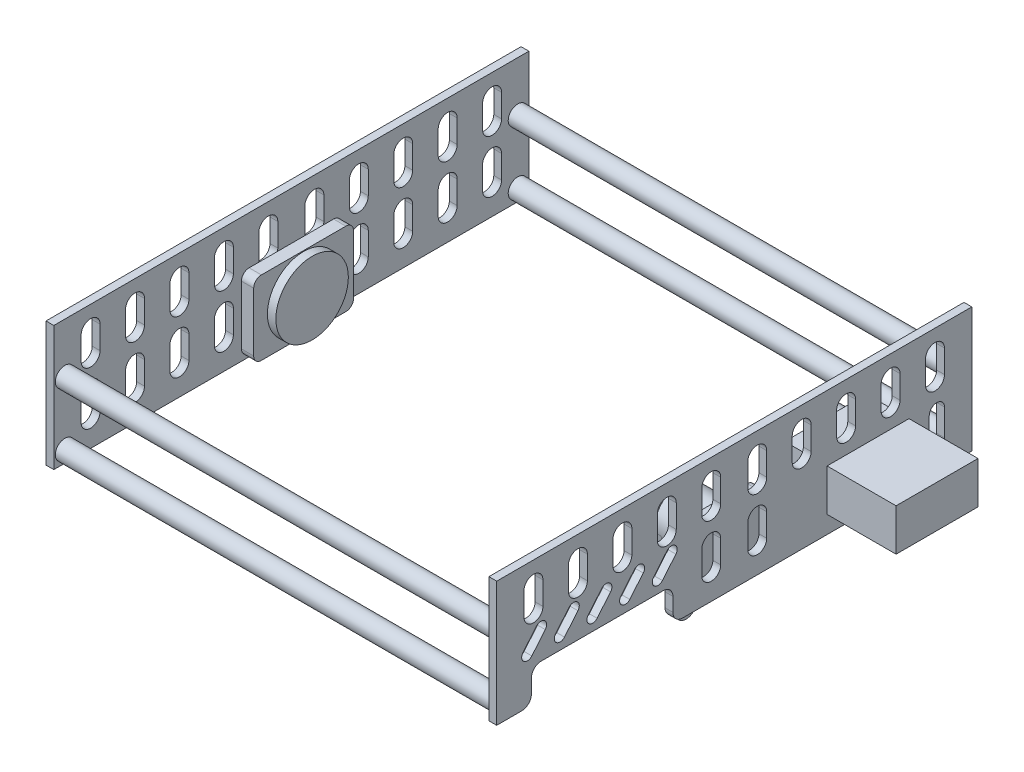
SolidWorks part; units mm, degrees
ref_plane "Front Plane" through (0, 0, 0) normal (0, 0, 1) x (1, 0, 0)
ref_plane "Top Plane" through (0, 0, 0) normal (0, 1, 0) x (1, 0, 0)
ref_plane "Right Plane" through (0, 0, 0) normal (1, 0, 0) x (0, 0, -1)
ref_plane "Plane1" through (12.7, 0, 0) normal (1, 0, 0) x (0, 0, -1)
sketch "Sketch1" plane through (0, 0, 0) normal (1, 0, 0) x (0, 0, -1)
  line L0 (0, 0) -> (0, -16.4338) construction
  line L1 (0, 0) -> (55.8004, 0) construction
  line L2 (0, -16.4338) -> (117.9322, -16.4338) construction
  line L3 (117.9322, -16.4338) -> (117.9322, 0) construction
  line L4 (-2.5019, -18.9357) -> (120.4341, -18.9357) construction
  line L5 (-2.5019, 2.5019) -> (120.4341, 2.5019) construction
  line L6 (-2.5019, 2.5019) -> (-2.5019, -18.9357) construction
  line L7 (120.4341, 2.5019) -> (120.4341, -18.9357) construction
  circle A0 centre (0, 0) radius 2.5019
  circle A1 centre (0, -16.4338) radius 2.5019
  circle A2 centre (117.9322, -16.4338) radius 2.5019
  circle A3 centre (117.9322, 0) radius 2.5019
  dimension "D2" = 5.0038
  dimension "D3" = 21.4376
  dimension "D4" = 122.936
extrude "Boss-Extrude1" add sketch "Sketch1" along normal blind 115.316
sketch "Sketch5" plane through (0, 0, 0) normal (1, 0, 0) x (0, 0, -1)
  line L4 (0, 0) -> (117.9322, -16.4338) construction
  line L5 (58.9661, 12.954) -> (58.9661, -19.558) construction
  line L6 (4.2291, -14.9987) -> (4.2291, 9.7028) construction
  line L8 (6.6941, 1.2458) -> (6.6941, 7.2378) construction
  line L10 (4.2291, 9.7028) -> (113.7031, 9.7028) construction
  line L15 (113.7031, -14.9987) -> (4.2291, -14.9987) construction
  line L20 (117.9322, 0) -> (0, -16.4338) construction
  line L29 (64.9581, 1.2458) -> (64.9581, 7.2378) construction
  line L38 (67.4231, 1.2458) -> (67.4231, 7.2378)
  line L45 (62.4931, 1.2458) -> (62.4931, 7.2378)
  line L52 (64.9581, -12.5337) -> (64.9581, -6.5417) construction
  line L61 (67.4231, -12.5337) -> (67.4231, -6.5417)
  line L70 (62.4931, -12.5337) -> (62.4931, -6.5417)
  line L76 (-2.8829, -19.558) -> (120.8151, -19.558)
  line L77 (-2.8829, -19.558) -> (-2.8829, 12.954)
  line L78 (-2.8829, 12.954) -> (120.8151, 12.954)
  line L79 (120.8151, -19.558) -> (120.8151, 12.954)
  line L80 (76.5281, -12.5337) -> (76.5281, -6.5417) construction
  line L81 (78.9931, -12.5337) -> (78.9931, -6.5417)
  line L82 (4.2291, 1.2458) -> (4.2291, 7.2378)
  line L83 (9.1591, 1.2458) -> (9.1591, 7.2378)
  line L84 (4.2291, 9.7028) -> (9.1591, 9.7028) construction
  line L85 (9.1591, 9.7028) -> (9.1591, -1.2192) construction
  line L86 (9.1591, -1.2192) -> (4.2291, -1.2192) construction
  line L87 (4.2291, -1.2192) -> (4.2291, 9.7028) construction
  line L88 (18.2641, 1.2458) -> (18.2641, 7.2378) construction
  line L89 (15.7991, 1.2458) -> (15.7991, 7.2378)
  line L90 (20.7291, 1.2458) -> (20.7291, 7.2378)
  line L91 (29.8341, 1.2458) -> (29.8341, 7.2378) construction
  line L92 (27.3691, 1.2458) -> (27.3691, 7.2378)
  line L93 (32.2991, 1.2458) -> (32.2991, 7.2378)
  line L94 (41.4041, 1.2458) -> (41.4041, 7.2378) construction
  line L95 (38.9391, 1.2458) -> (38.9391, 7.2378)
  line L96 (43.8691, 1.2458) -> (43.8691, 7.2378)
  line L97 (52.9741, 1.2458) -> (52.9741, 7.2378) construction
  line L98 (50.5091, 1.2458) -> (50.5091, 7.2378)
  line L99 (55.4391, 1.2458) -> (55.4391, 7.2378)
  line L100 (18.2641, -12.5337) -> (18.2641, -6.5417) construction
  line L101 (15.7991, -12.5337) -> (15.7991, -6.5417)
  line L102 (20.7291, -12.5337) -> (20.7291, -6.5417)
  line L103 (29.8341, -12.5337) -> (29.8341, -6.5417) construction
  line L104 (27.3691, -12.5337) -> (27.3691, -6.5417)
  line L105 (32.2991, -12.5337) -> (32.2991, -6.5417)
  line L106 (41.4041, -12.5337) -> (41.4041, -6.5417) construction
  line L107 (38.9391, -12.5337) -> (38.9391, -6.5417)
  line L108 (43.8691, -12.5337) -> (43.8691, -6.5417)
  line L109 (52.9741, -12.5337) -> (52.9741, -6.5417) construction
  line L110 (50.5091, -12.5337) -> (50.5091, -6.5417)
  line L111 (55.4391, -12.5337) -> (55.4391, -6.5417)
  line L112 (6.6941, -12.5337) -> (6.6941, -6.5417) construction
  line L113 (4.2291, -12.5337) -> (4.2291, -6.5417)
  line L114 (9.1591, -12.5337) -> (9.1591, -6.5417)
  line L116 (74.0631, -12.5337) -> (74.0631, -6.5417)
  line L117 (113.7031, 9.7028) -> (113.7031, -14.9987) construction
  line L118 (76.5281, 1.2458) -> (76.5281, 7.2378) construction
  line L119 (78.9931, 1.2458) -> (78.9931, 7.2378)
  line L120 (74.0631, 1.2458) -> (74.0631, 7.2378)
  line L121 (88.0981, 1.2458) -> (88.0981, 7.2378) construction
  line L122 (90.5631, 1.2458) -> (90.5631, 7.2378)
  line L123 (85.6331, 1.2458) -> (85.6331, 7.2378)
  line L124 (88.0981, -12.5337) -> (88.0981, -6.5417) construction
  line L125 (90.5631, -12.5337) -> (90.5631, -6.5417)
  line L126 (85.6331, -12.5337) -> (85.6331, -6.5417)
  line L127 (99.6681, -12.5337) -> (99.6681, -6.5417) construction
  line L128 (102.1331, -12.5337) -> (102.1331, -6.5417)
  line L129 (97.2031, -12.5337) -> (97.2031, -6.5417)
  line L130 (99.6681, 1.2458) -> (99.6681, 7.2378) construction
  line L131 (102.1331, 1.2458) -> (102.1331, 7.2378)
  line L132 (97.2031, 1.2458) -> (97.2031, 7.2378)
  line L133 (111.2381, 1.2458) -> (111.2381, 7.2378) construction
  line L134 (113.7031, 1.2458) -> (113.7031, 7.2378)
  line L135 (108.7731, 1.2458) -> (108.7731, 7.2378)
  line L136 (111.2381, -12.5337) -> (111.2381, -6.5417) construction
  line L137 (113.7031, -12.5337) -> (113.7031, -6.5417)
  line L138 (108.7731, -12.5337) -> (108.7731, -6.5417)
  line L140 (-6.1459, 2.5019) -> (0, 2.5019) construction
  arc A40 (4.2291, 1.2458) -> (9.1591, 1.2458) centre (6.6941, 1.2458) ccw
  arc A41 (9.1591, 7.2378) -> (4.2291, 7.2378) centre (6.6941, 7.2378) ccw
  arc A42 (15.7991, 1.2458) -> (20.7291, 1.2458) centre (18.2641, 1.2458) ccw
  arc A43 (20.7291, 7.2378) -> (15.7991, 7.2378) centre (18.2641, 7.2378) ccw
  arc A44 (27.3691, 1.2458) -> (32.2991, 1.2458) centre (29.8341, 1.2458) ccw
  arc A45 (32.2991, 7.2378) -> (27.3691, 7.2378) centre (29.8341, 7.2378) ccw
  arc A46 (38.9391, 1.2458) -> (43.8691, 1.2458) centre (41.4041, 1.2458) ccw
  arc A47 (43.8691, 7.2378) -> (38.9391, 7.2378) centre (41.4041, 7.2378) ccw
  arc A48 (50.5091, 1.2458) -> (55.4391, 1.2458) centre (52.9741, 1.2458) ccw
  arc A49 (55.4391, 7.2378) -> (50.5091, 7.2378) centre (52.9741, 7.2378) ccw
  arc A50 (15.7991, -12.5337) -> (20.7291, -12.5337) centre (18.2641, -12.5337) ccw
  arc A51 (20.7291, -6.5417) -> (15.7991, -6.5417) centre (18.2641, -6.5417) ccw
  arc A52 (27.3691, -12.5337) -> (32.2991, -12.5337) centre (29.8341, -12.5337) ccw
  arc A53 (32.2991, -6.5417) -> (27.3691, -6.5417) centre (29.8341, -6.5417) ccw
  arc A54 (38.9391, -12.5337) -> (43.8691, -12.5337) centre (41.4041, -12.5337) ccw
  arc A55 (43.8691, -6.5417) -> (38.9391, -6.5417) centre (41.4041, -6.5417) ccw
  arc A56 (50.5091, -12.5337) -> (55.4391, -12.5337) centre (52.9741, -12.5337) ccw
  arc A57 (55.4391, -6.5417) -> (50.5091, -6.5417) centre (52.9741, -6.5417) ccw
  arc A58 (4.2291, -12.5337) -> (9.1591, -12.5337) centre (6.6941, -12.5337) ccw
  arc A59 (9.1591, -6.5417) -> (4.2291, -6.5417) centre (6.6941, -6.5417) ccw
  circle A60 centre (0, 0) radius 2.5019 construction
  circle A61 centre (0, -16.4338) radius 2.5019 construction
  circle A62 centre (117.9322, 0) radius 2.5019 construction
  circle A63 centre (117.9322, -16.4338) radius 2.5019 construction
  arc A64 (67.4231, 1.2458) -> (62.4931, 1.2458) centre (64.9581, 1.2458) cw
  arc A65 (62.4931, 7.2378) -> (67.4231, 7.2378) centre (64.9581, 7.2378) cw
  arc A66 (67.4231, -12.5337) -> (62.4931, -12.5337) centre (64.9581, -12.5337) cw
  arc A67 (62.4931, -6.5417) -> (67.4231, -6.5417) centre (64.9581, -6.5417) cw
  arc A68 (78.9931, -12.5337) -> (74.0631, -12.5337) centre (76.5281, -12.5337) cw
  arc A69 (74.0631, -6.5417) -> (78.9931, -6.5417) centre (76.5281, -6.5417) cw
  arc A70 (78.9931, 1.2458) -> (74.0631, 1.2458) centre (76.5281, 1.2458) cw
  arc A71 (74.0631, 7.2378) -> (78.9931, 7.2378) centre (76.5281, 7.2378) cw
  arc A72 (90.5631, 1.2458) -> (85.6331, 1.2458) centre (88.0981, 1.2458) cw
  arc A73 (85.6331, 7.2378) -> (90.5631, 7.2378) centre (88.0981, 7.2378) cw
  arc A74 (90.5631, -12.5337) -> (85.6331, -12.5337) centre (88.0981, -12.5337) cw
  arc A75 (85.6331, -6.5417) -> (90.5631, -6.5417) centre (88.0981, -6.5417) cw
  arc A76 (102.1331, -12.5337) -> (97.2031, -12.5337) centre (99.6681, -12.5337) cw
  arc A77 (97.2031, -6.5417) -> (102.1331, -6.5417) centre (99.6681, -6.5417) cw
  arc A78 (102.1331, 1.2458) -> (97.2031, 1.2458) centre (99.6681, 1.2458) cw
  arc A79 (97.2031, 7.2378) -> (102.1331, 7.2378) centre (99.6681, 7.2378) cw
  arc A80 (113.7031, 1.2458) -> (108.7731, 1.2458) centre (111.2381, 1.2458) cw
  arc A81 (108.7731, 7.2378) -> (113.7031, 7.2378) centre (111.2381, 7.2378) cw
  arc A82 (113.7031, -12.5337) -> (108.7731, -12.5337) centre (111.2381, -12.5337) cw
  arc A83 (108.7731, -6.5417) -> (113.7031, -6.5417) centre (111.2381, -6.5417) cw
  point P15 (58.9661, -8.2169)
  point P19 (64.9581, 4.2418)
  point P26 (64.9581, -9.5377)
  point P36 (76.5281, -9.5377)
  point P43 (76.5281, 4.2418)
  point P50 (88.0981, 4.2418)
  point P57 (88.0981, -9.5377)
  point P64 (99.6681, -9.5377)
  point P71 (99.6681, 4.2418)
  point P78 (111.2381, 4.2418)
  point P88 (111.2381, -9.5377)
  point P100 (58.9661, -7.9692)
  point P166 (6.6941, 4.2418)
  point P180 (18.2641, 4.2418)
  point P187 (29.8341, 4.2418)
  point P194 (41.4041, 4.2418)
  point P201 (52.9741, 4.2418)
  point P208 (18.2641, -9.5377)
  point P215 (29.8341, -9.5377)
  point P222 (41.4041, -9.5377)
  point P229 (52.9741, -9.5377)
  point P236 (6.6941, -9.5377)
  dimension "D3" = 123.698
  dimension "D2" = 16.5
  dimension "D4" = 10.4521
  dimension "D11" = 32.512
  dimension "D13" = 3.2512
  dimension "D14" = 7.112
  dimension "D15" = 4.93
  dimension "D16" = 10.922
  dimension "D19" = 13.7795
  dimension "D17" = 5
  dimension "D18" = 2
extrude "Boss-Extrude3" add sketch "Sketch5" along normal blind 2.032
ref_plane "Plane2" through (115.316, 0, 0) normal (1, 0, 0) x (0, 0, -1)
sketch "Sketch6" plane through (115.316, 0, 0) normal (1, 0, 0) x (0, 0, -1)
  line L0 (120.8151, 12.954) -> (-2.8829, 12.954) construction
  line L1 (-2.8829, -19.558) -> (3.6195, -19.558)
  line L2 (-2.8829, -19.558) -> (-2.8829, 12.954)
  line L3 (-2.8829, 12.954) -> (120.8151, 12.954)
  line L4 (120.8151, -19.558) -> (120.8151, 12.954)
  line L5 (-2.8829, -19.558) -> (120.8151, 12.954) construction
  line L6 (-2.8829, 12.954) -> (120.8151, -19.558) construction
  line L7 (-2.8829, 12.954) -> (-2.8829, -19.558) construction
  line L8 (6.1595, -17.018) -> (6.1595, -13.4112)
  line L9 (8.6995, -10.8712) -> (40.4495, -10.8712)
  line L10 (42.9895, -13.4112) -> (42.9895, -17.018)
  line L11 (45.5295, -19.558) -> (120.8151, -19.558)
  line L12 (52.9741, -6.5417) -> (52.9741, -12.5337) construction
  line L13 (55.4391, -6.5417) -> (55.4391, -12.5337)
  line L14 (50.5091, -6.5417) -> (50.5091, -12.5337)
  line L15 (64.9581, -6.5417) -> (64.9581, -12.5337) construction
  line L16 (67.4231, -6.5417) -> (67.4231, -12.5337)
  line L17 (62.4931, -6.5417) -> (62.4931, -12.5337)
  line L18 (111.7192, -6.0606) -> (111.7192, -13.0148) construction
  line L19 (113.7031, -6.0606) -> (113.7031, -13.0148)
  line L20 (109.7354, -6.0606) -> (109.7354, -13.0148)
  line L21 (113.7031, -4.0767) -> (50.5091, -4.0767) construction
  line L22 (50.5091, -4.0767) -> (50.5091, -14.9987) construction
  line L23 (50.5091, -14.9987) -> (113.7031, -14.9987) construction
  line L24 (113.7031, -14.9987) -> (113.7031, -4.0767) construction
  line L25 (113.7031, -12.5337) -> (113.7031, -6.5417) construction
  line L27 (104.4658, -4.0767) -> (83.1362, -4.0767)
  line L28 (104.4658, -4.0767) -> (104.4658, -14.9987)
  line L29 (104.4658, -14.9987) -> (83.1362, -14.9987)
  line L30 (83.1362, -4.0767) -> (83.1362, -14.9987)
  line L31 (104.4658, -4.0767) -> (83.1362, -14.9987) construction
  line L32 (104.4658, -14.9987) -> (83.1362, -4.0767) construction
  line L88 (15.7991, 7.2378) -> (15.7991, 1.2458)
  line L89 (20.7291, 1.2458) -> (20.7291, 7.2378)
  line L90 (9.1591, 1.2458) -> (9.1591, 7.2378)
  line L91 (4.2291, 7.2378) -> (4.2291, 1.2458)
  line L92 (9.1591, 1.2458) -> (9.1591, 7.2378)
  line L93 (4.2291, 7.2378) -> (4.2291, 1.2458)
  line L94 (27.3691, 7.2378) -> (27.3691, 1.2458)
  line L95 (32.2991, 1.2458) -> (32.2991, 7.2378)
  line L96 (38.9391, 7.2378) -> (38.9391, 1.2458)
  line L97 (43.8691, 1.2458) -> (43.8691, 7.2378)
  line L98 (50.5091, 7.2378) -> (50.5091, 1.2458)
  line L99 (55.4391, 1.2458) -> (55.4391, 7.2378)
  line L100 (15.7991, 7.2378) -> (15.7991, 1.2458) construction
  line L101 (58.9661, 12.954) -> (58.9661, -19.558) construction
  line L102 (62.4931, 1.2458) -> (62.4931, 7.2378)
  line L103 (67.4231, 7.2378) -> (67.4231, 1.2458)
  line L104 (74.0631, 1.2458) -> (74.0631, 7.2378)
  line L105 (78.9931, 7.2378) -> (78.9931, 1.2458)
  line L106 (85.6331, 1.2458) -> (85.6331, 7.2378)
  line L107 (90.5631, 7.2378) -> (90.5631, 1.2458)
  line L108 (97.2031, 1.2458) -> (97.2031, 7.2378)
  line L109 (102.1331, 7.2378) -> (102.1331, 1.2458)
  line L110 (113.7031, 7.2378) -> (113.7031, 1.2458)
  line L111 (108.7731, 1.2458) -> (108.7731, 7.2378)
  arc A0 (55.4391, -6.5417) -> (50.5091, -6.5417) centre (52.9741, -6.5417) ccw
  arc A1 (50.5091, -12.5337) -> (55.4391, -12.5337) centre (52.9741, -12.5337) ccw
  arc A4 (67.4231, -6.5417) -> (62.4931, -6.5417) centre (64.9581, -6.5417) ccw
  arc A6 (62.4931, -12.5337) -> (67.4231, -12.5337) centre (64.9581, -12.5337) ccw
  arc A10 (55.4391, -6.5417) -> (50.5091, -6.5417) centre (52.9741, -6.5417) ccw construction
  arc A11 (50.5091, -12.5337) -> (55.4391, -12.5337) centre (52.9741, -12.5337) ccw construction
  arc A12 (67.4231, -6.5417) -> (62.4931, -6.5417) centre (64.9581, -6.5417) ccw construction
  arc A13 (62.4931, -12.5337) -> (67.4231, -12.5337) centre (64.9581, -12.5337) ccw construction
  arc A14 (113.7031, -6.0606) -> (109.7354, -6.0606) centre (111.7192, -6.0606) ccw
  arc A15 (109.7354, -13.0148) -> (113.7031, -13.0148) centre (111.7192, -13.0148) ccw
  arc A70 (20.7291, 7.2378) -> (15.7991, 7.2378) centre (18.2641, 7.2378) ccw
  arc A71 (15.7991, 1.2458) -> (20.7291, 1.2458) centre (18.2641, 1.2458) ccw
  arc A72 (4.2291, 1.2458) -> (9.1591, 1.2458) centre (6.6941, 1.2458) ccw
  arc A73 (9.1591, 7.2378) -> (4.2291, 7.2378) centre (6.6941, 7.2378) ccw
  arc A74 (4.2291, 1.2458) -> (9.1591, 1.2458) centre (6.6941, 1.2458) ccw
  arc A75 (9.1591, 7.2378) -> (4.2291, 7.2378) centre (6.6941, 7.2378) ccw
  arc A76 (32.2991, 7.2378) -> (27.3691, 7.2378) centre (29.8341, 7.2378) ccw
  arc A77 (27.3691, 1.2458) -> (32.2991, 1.2458) centre (29.8341, 1.2458) ccw
  arc A78 (43.8691, 7.2378) -> (38.9391, 7.2378) centre (41.4041, 7.2378) ccw
  arc A79 (38.9391, 1.2458) -> (43.8691, 1.2458) centre (41.4041, 1.2458) ccw
  arc A80 (55.4391, 7.2378) -> (50.5091, 7.2378) centre (52.9741, 7.2378) ccw
  arc A81 (50.5091, 1.2458) -> (55.4391, 1.2458) centre (52.9741, 1.2458) ccw
  arc A82 (62.4931, 7.2378) -> (67.4231, 7.2378) centre (64.9581, 7.2378) cw
  arc A83 (67.4231, 1.2458) -> (62.4931, 1.2458) centre (64.9581, 1.2458) cw
  arc A84 (74.0631, 7.2378) -> (78.9931, 7.2378) centre (76.5281, 7.2378) cw
  arc A85 (78.9931, 1.2458) -> (74.0631, 1.2458) centre (76.5281, 1.2458) cw
  arc A86 (85.6331, 7.2378) -> (90.5631, 7.2378) centre (88.0981, 7.2378) cw
  arc A87 (90.5631, 1.2458) -> (85.6331, 1.2458) centre (88.0981, 1.2458) cw
  arc A88 (97.2031, 7.2378) -> (102.1331, 7.2378) centre (99.6681, 7.2378) cw
  arc A89 (102.1331, 1.2458) -> (97.2031, 1.2458) centre (99.6681, 1.2458) cw
  arc A90 (108.7731, 7.2378) -> (113.7031, 7.2378) centre (111.2381, 7.2378) cw
  arc A91 (113.7031, 1.2458) -> (108.7731, 1.2458) centre (111.2381, 1.2458) cw
  arc A92 (42.9895, -17.018) -> (45.5295, -19.558) centre (45.5295, -17.018) ccw
  arc A93 (40.4495, -10.8712) -> (42.9895, -13.4112) centre (40.4495, -13.4112) cw
  arc A94 (6.1595, -13.4112) -> (8.6995, -10.8712) centre (8.6995, -13.4112) cw
  arc A95 (6.1595, -17.018) -> (3.6195, -19.558) centre (3.6195, -17.018) cw
  point P0 (58.9661, -3.302)
  point P79 (42.9895, -19.558)
  point P82 (42.9895, -10.8712)
  point P85 (6.1595, -10.8712)
  point P88 (6.1595, -19.558)
  point P91 (52.9741, -9.5377)
  point P96 (64.9581, -9.5377)
  point P117 (111.7192, -9.5377)
  point P128 (93.801, -9.5377)
  dimension "D6" = 2.54
  dimension "D3" = 8.6868
  dimension "D4" = 36.83
  dimension "D5" = 9.0424
  dimension "D1" = 0
  dimension "D2" = 5
extrude "Boss-Extrude4" add sketch "Sketch6" along normal blind 2.032 separate body
sketch "Sketch7" plane through (117.348, 0, 0) normal (1, 0, 0) x (0, 0, -1)
  line L0 (5.1171, -7.5212) -> (8.6171, -3.326) construction
  line L1 (3.9653, -6.5603) -> (7.4653, -2.3651)
  line L2 (6.2689, -8.4821) -> (9.7689, -4.2869)
  line L3 (13.6171, -7.5212) -> (17.1171, -3.326) construction
  line L4 (12.4653, -6.5603) -> (15.9653, -2.3651)
  line L5 (14.7689, -8.4821) -> (18.2689, -4.2869)
  line L6 (22.1171, -7.5212) -> (25.6171, -3.326) construction
  line L7 (20.9653, -6.5603) -> (24.4653, -2.3651)
  line L8 (23.2689, -8.4821) -> (26.7689, -4.2869)
  line L9 (30.6171, -7.5212) -> (34.1171, -3.326) construction
  line L10 (29.4653, -6.5603) -> (32.9653, -2.3651)
  line L11 (31.7689, -8.4821) -> (35.2689, -4.2869)
  line L12 (39.1171, -7.5212) -> (42.6171, -3.326) construction
  line L13 (37.9653, -6.5603) -> (41.4653, -2.3651)
  line L14 (40.2689, -8.4821) -> (43.7689, -4.2869)
  line L15 (44.1171, -9.0212) -> (3.6171, -9.0212) construction
  line L16 (8.6995, -10.8712) -> (40.4495, -10.8712) construction
  line L17 (3.6171, -9.0212) -> (3.6171, -1.826) construction
  line L18 (-2.8829, 12.954) -> (-2.8829, -19.558) construction
  line L19 (3.6171, -1.826) -> (44.1171, -1.826) construction
  line L20 (44.1171, -1.826) -> (44.1171, -9.0212) construction
  line L21 (120.8151, 12.954) -> (-2.8829, 12.954) construction
  line L22 (10.1171, -1.826) -> (10.1171, -9.0212) construction
  arc A0 (3.9653, -6.5603) -> (6.2689, -8.4821) centre (5.1171, -7.5212) ccw
  arc A1 (9.7689, -4.2869) -> (7.4653, -2.3651) centre (8.6171, -3.326) ccw
  arc A2 (12.4653, -6.5603) -> (14.7689, -8.4821) centre (13.6171, -7.5212) ccw
  arc A3 (18.2689, -4.2869) -> (15.9653, -2.3651) centre (17.1171, -3.326) ccw
  arc A4 (20.9653, -6.5603) -> (23.2689, -8.4821) centre (22.1171, -7.5212) ccw
  arc A5 (26.7689, -4.2869) -> (24.4653, -2.3651) centre (25.6171, -3.326) ccw
  arc A6 (29.4653, -6.5603) -> (31.7689, -8.4821) centre (30.6171, -7.5212) ccw
  arc A7 (35.2689, -4.2869) -> (32.9653, -2.3651) centre (34.1171, -3.326) ccw
  arc A8 (37.9653, -6.5603) -> (40.2689, -8.4821) centre (39.1171, -7.5212) ccw
  arc A9 (43.7689, -4.2869) -> (41.4653, -2.3651) centre (42.6171, -3.326) ccw
  point P2 (6.8671, -5.4236)
  point P10 (15.3671, -5.4236)
  point P17 (23.8671, -5.4236)
  point P24 (32.3671, -5.4236)
  point P31 (40.8671, -5.4236)
  dimension "D2" = 3
  dimension "D3" = 1.85
  dimension "D4" = 6.5
  dimension "D5" = 14.78
  dimension "D6" = 40.5
  dimension "D7" = 6.5
  dimension "D1" = 5
extrude "Cut-Extrude1" cut sketch "Sketch7" against normal up to surface (2.032 mm away) up to face at (115.316, -11.2437, -36.0384)
sketch "Sketch8" plane through (115.316, 0, 0) normal (-1, 0, 0) x (0, 0, 1)
  line L0 (-67.4231, -9.5377) -> (-50.5091, -9.5377) construction
  line L1 (-67.3513, -16.3825) -> (-50.5809, -16.3825)
  line L2 (-69.3513, -14.3825) -> (-69.3513, -4.6929)
  line L3 (-67.3513, -2.6929) -> (-50.5809, -2.6929)
  line L4 (-48.5809, -14.3825) -> (-48.5809, -4.6929)
  line L5 (-69.3513, -16.3825) -> (-48.5809, -2.6929) construction
  line L6 (-69.3513, -2.6929) -> (-48.5809, -16.3825) construction
  line L7 (-67.4231, -12.5337) -> (-67.4231, -6.5417) construction
  line L8 (-50.5091, -6.5417) -> (-50.5091, -12.5337) construction
  arc A0 (-67.3513, -16.3825) -> (-69.3513, -14.3825) centre (-67.3513, -14.3825) cw
  arc A1 (-50.5809, -16.3825) -> (-48.5809, -14.3825) centre (-50.5809, -14.3825) ccw
  arc A2 (-50.5809, -2.6929) -> (-48.5809, -4.6929) centre (-50.5809, -4.6929) cw
  arc A3 (-69.3513, -4.6929) -> (-67.3513, -2.6929) centre (-67.3513, -4.6929) cw
  point P0 (-58.9661, -9.5377)
  dimension "D1" = 2
extrude "Boss-Extrude5" add sketch "Sketch8" along normal blind 3
sketch "Sketch16" plane through (2.032, 0, 0) normal (1, 0, 0) x (0, 0, -1)
  line L0 (55.4391, -12.5337) -> (62.4931, -12.5337) construction
  line L1 (47.9661, -18.758) -> (69.9661, -18.758)
  line L2 (45.9661, -16.758) -> (45.9661, -1.4767)
  line L3 (47.9661, 0.5233) -> (69.9661, 0.5233)
  line L4 (71.9661, -16.758) -> (71.9661, -1.4767)
  line L5 (45.9661, -18.758) -> (71.9661, 0.5233) construction
  line L6 (45.9661, 0.5233) -> (71.9661, -18.758) construction
  line L9 (62.4931, -12.5337) -> (58.9661, -12.5337) construction
  line L10 (58.9661, -12.5337) -> (58.9661, 0.5233) construction
  line L11 (-2.8829, -19.558) -> (120.8151, -19.558) construction
  line L12 (52.9741, -4.0767) -> (64.9581, -4.0767) construction
  arc A0 (69.9661, 0.5233) -> (71.9661, -1.4767) centre (69.9661, -1.4767) cw
  arc A1 (69.9661, -18.758) -> (71.9661, -16.758) centre (69.9661, -16.758) ccw
  arc A2 (47.9661, -18.758) -> (45.9661, -16.758) centre (47.9661, -16.758) cw
  arc A3 (45.9661, -1.4767) -> (47.9661, 0.5233) centre (47.9661, -1.4767) cw
  arc A4 (55.4391, -6.5417) -> (50.5091, -6.5417) centre (52.9741, -6.5417) ccw construction
  arc A5 (67.4231, -6.5417) -> (62.4931, -6.5417) centre (64.9581, -6.5417) ccw construction
  point P0 (58.9661, -9.1174)
  dimension "D1" = 2
  dimension "D2" = 0.8
  dimension "D3" = 4.6
  dimension "D4" = 26
extrude "Boss-Extrude12" add sketch "Sketch16" along normal blind 3.2
sketch "Sketch17" plane through (5.232, 0, 0) normal (1, 0, 0) x (0, 0, -1)
  line L0 (45.9661, -9.1173) -> (71.9661, -9.1173) construction
  line L1 (45.9661, -1.4767) -> (45.9661, -16.758) construction
  line L2 (71.9661, -16.758) -> (71.9661, -1.4767) construction
  line L3 (58.9661, 0.3233) -> (70.8379, 0.3233) construction
  line L4 (69.9661, 0.5233) -> (47.9661, 0.5233) construction
  circle A0 centre (58.9661, -9.1174) radius 9.4407
  arc A1 (71.9661, -1.4767) -> (69.9661, 0.5233) centre (69.9661, -1.4767) ccw construction
  dimension "D1" = 0.2
extrude "Boss-Extrude13" add sketch "Sketch17" along normal blind 2.2
sketch "Sketch9" plane through (112.316, 0, 0) normal (-1, 0, 0) x (0, 0, 1)
  line L0 (-58.9661, -2.6929) -> (-58.9661, -16.3825) construction
  line L1 (-50.5809, -2.6929) -> (-67.3513, -2.6929) construction
  line L2 (-67.3513, -16.3825) -> (-50.5809, -16.3825) construction
  line L4 (-58.9661, -2.8929) -> (-68.2231, -2.8929) construction
  line L6 (-50.5809, -2.6929) -> (-67.3513, -2.6929) construction
  circle A0 centre (-58.9661, -9.5377) radius 6.6448
  arc A3 (-67.3513, -2.6929) -> (-69.3513, -4.6929) centre (-67.3513, -4.6929) ccw construction
  dimension "D1" = 0.2
extrude "Boss-Extrude6" add sketch "Sketch9" along normal blind 9
sketch "Sketch10" plane through (103.316, 0, 0) normal (-1, 0, 0) x (0, 0, 1)
  line L2 (-58.9661, -22.1504) -> (-58.9661, -9.5377) construction
  line L3 (-65.4876, -10.8118) -> (-61.616, -30.6295)
  line L5 (-65.4876, -10.8118) -> (-52.4446, -10.8118)
  line L6 (-56.3162, -30.6295) -> (-52.4446, -10.8118)
  line L7 (-61.616, -30.6295) -> (-56.3162, -30.6295) construction
  line L8 (-58.9661, -32.8118) -> (-55.7901, -32.8118) construction
  circle A0 centre (-58.9661, -9.5377) radius 6.6448 construction
  circle A3 centre (-58.9661, -9.5377) radius 6.6448 construction
  arc A4 (-61.616, -30.6295) -> (-56.3162, -30.6295) centre (-58.9661, -30.1118) ccw
  dimension "D2" = 2.7
  dimension "D1" = 22
extrude "Boss-Extrude7" add sketch "Sketch10" against normal blind 1.5
ref_plane "Plane3" through (115.316, -4.0767, -104.4658) normal (0, 0, 1) x (1, 0, 0)
sketch "Sketch12" plane through (0, -4.0767, 0) normal (0, -1, 0) x (1, 0, 0)
  line L0 (115.316, -83.1362) -> (115.316, -80.8362)
  line L1 (115.316, -80.8362) -> (113.616, -80.8362)
  line L2 (113.616, -80.8362) -> (113.616, -83.1362)
  line L3 (113.616, -83.1362) -> (106.316, -83.1362)
  line L4 (106.316, -83.1362) -> (106.316, -104.4658)
  line L11 (135.316, -104.4658) -> (135.316, -83.1362)
  line L12 (135.316, -83.1362) -> (115.316, -83.1362)
  line L13 (115.316, -93.801) -> (106.316, -93.801) construction
  line L14 (115.316, -104.4658) -> (115.316, -83.1362) construction
  line L15 (135.316, -104.4658) -> (115.316, -104.4658)
  line L16 (115.316, -104.4658) -> (115.316, -106.7658)
  line L17 (115.316, -106.7658) -> (113.616, -106.7658)
  line L18 (113.616, -106.7658) -> (113.616, -104.4658)
  line L19 (113.616, -104.4658) -> (106.316, -104.4658)
  point P17 (135.316, -93.801)
  dimension "D1" = 1.7
  dimension "D2" = 9
  dimension "D3" = 2.3
  dimension "D4" = 20
extrude "Boss-Extrude8" add sketch "Sketch12" along normal up to surface (10.922 mm away) up to face at (116.332, -14.9987, -93.801)
sketch "Sketch13" plane through (106.316, 0, 0) normal (-1, 0, 0) x (0, 0, 1)
  line L0 (-104.4658, -9.5377) -> (-83.1362, -9.5377) construction
  line L1 (-104.4658, -14.9987) -> (-104.4658, -4.0767) construction
  line L2 (-83.1362, -14.9987) -> (-83.1362, -4.0767) construction
  line L3 (-103.7658, -9.5377) -> (-103.7658, -4.0767) construction
  line L4 (-83.1362, -4.0767) -> (-104.4658, -4.0767) construction
  circle A0 centre (-99.7658, -9.5377) radius 4
  dimension "D1" = 8
  dimension "D2" = 0.7
extrude "Boss-Extrude9" add sketch "Sketch13" along normal blind 0.7
sketch "Sketch15" plane through (105.616, 0, 0) normal (-1, 0, 0) x (0, 0, 1)
  circle A0 centre (-99.7658, -9.5377) radius 3.25
  circle A1 centre (-99.7658, -9.5377) radius 4 construction
  dimension "D1" = 6.5
extrude "Boss-Extrude10" add sketch "Sketch15" along normal blind 3.7
sketch "Sketch14" plane through (101.916, 0, 0) normal (-1, 0, 0) x (0, 0, 1)
  line L0 (-58.9661, -32.8118) -> (-97.4687, -32.8118) construction
  line L1 (-97.4687, -32.8118) -> (-97.4687, -28.6269) construction
  line L2 (-99.7658, -30.8118) -> (-99.7658, -28.5118) construction
  line L3 (-99.7658, -9.5377) -> (-99.7658, -6.2877) construction
  line L4 (-99.7658, -6.2877) -> (-80.8362, -6.2877) construction
  line L5 (-99.7658, -30.8118) -> (-97.4687, -30.8118) construction
  line L6 (-99.7658, -9.5377) -> (-99.7658, -28.5118) construction
  line L7 (-102.0629, -28.6269) -> (-103.0117, -9.7004)
  line L8 (-96.5199, -9.7004) -> (-97.4687, -28.6269)
  line L9 (-80.8362, -14.9987) -> (-80.8362, -4.0767) construction
  arc A2 (-97.4687, -28.6269) -> (-102.0629, -28.6269) centre (-99.7658, -28.5118) cw
  arc A4 (-103.0117, -9.7004) -> (-96.5199, -9.7004) centre (-99.7658, -9.5377) cw
  arc A5 (-61.616, -30.6295) -> (-56.3162, -30.6295) centre (-58.9661, -30.1118) ccw construction
  circle A7 centre (-99.7658, -9.5377) radius 3.25 construction
  dimension "D2" = 4.6
  dimension "D3" = 2
extrude "Boss-Extrude11" add sketch "Sketch14" along normal blind 1.2 contours L7 A4 L8 A2
hole_wizard "Hole2" positions "3DSketch1" profile "Sketch18" legacy
sketch3d "3DSketch1"
  line L0 (100.716, -28.6269, -97.4687) -> (100.716, -28.6269, -102.0629) construction
  line L2 (103.316, -30.6295, -56.3162) -> (103.316, -30.6295, -61.616) construction
  point P0 (100.716, -28.6269, -99.7658)
  point P2 (103.316, -30.6295, -58.9661)
sketch "Sketch18" plane through (100.716, -28.6269, -99.7658) normal (0, 1, 0) x (0, 0, 1)
  line L0 (0, 0) -> (0, 20)
  line L1 (0, 20) -> (1, 20)
  line L2 (1, 20) -> (1, 0)
  line L3 (1, 0) -> (0, 0)
  line L4 (0, 110) -> (0, -10) construction
  dimension "Diameter" = 2
  dimension "Depth" = 20
equation "\"x\"= 5cm"
